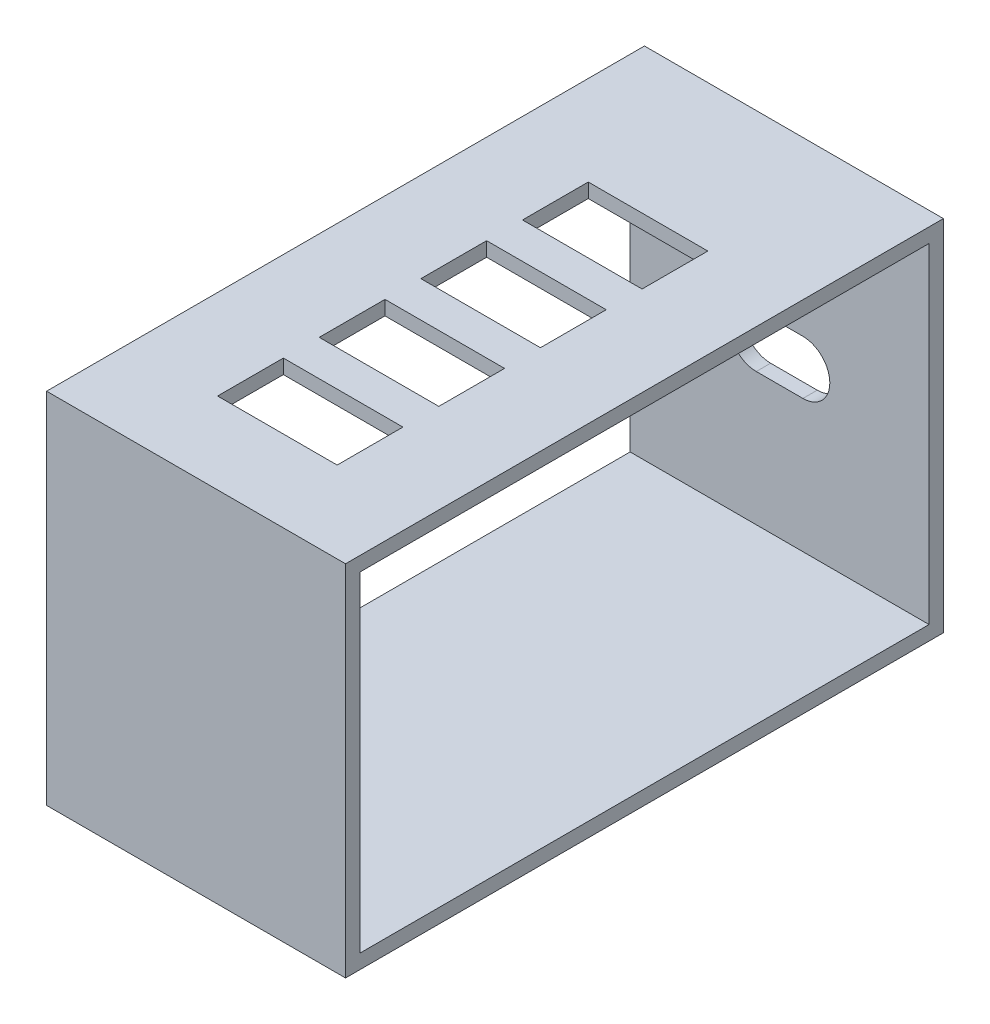
SolidWorks part; units mm, degrees
ref_plane "Front Plane" through (0, 0, 0) normal (0, 0, 1) x (1, 0, 0)
ref_plane "Top Plane" through (0, 0, 0) normal (0, 1, 0) x (1, 0, 0)
ref_plane "Right Plane" through (0, 0, 0) normal (1, 0, 0) x (0, 0, -1)
sketch "Sketch1" plane through (0, 0, 0) normal (1, 0, 0) x (0, 0, -1)
  line L1 (-25, -15) -> (25, -15)
  line L2 (-25, -15) -> (-25, 15)
  line L3 (-25, 15) -> (25, 15)
  line L4 (25, -15) -> (25, 15)
  line L5 (-25, -15) -> (25, 15) construction
  line L6 (-25, 15) -> (25, -15) construction
  point P0 (0, 0)
  dimension "D1" = 50
  dimension "D2" = 30
extrude "Boss-Extrude1" add sketch "Sketch1" along normal mid plane 25
sketch "Sketch2" plane through (-12.5, 0, 0) normal (-1, 0, 0) x (0, 0, 1)
  line L8 (-23.8, 13.8) -> (-23.8, -13.8)
  line L9 (-23.8, -13.8) -> (23.8, -13.8)
  line L10 (23.8, -13.8) -> (23.8, 13.8)
  line L11 (23.8, 13.8) -> (-23.8, 13.8)
  line L12 (-23.8, 13.8) -> (-23.8, -13.8)
  line L13 (-23.8, -13.8) -> (23.8, -13.8)
  line L14 (23.8, -13.8) -> (23.8, 13.8)
  line L15 (23.8, 13.8) -> (-23.8, 13.8)
  dimension "D1" = 1.2
extrude "Cut-Extrude1" cut sketch "Sketch2" against normal up to surface (25 mm away) up to face at (12.5, 0, 0)
sketch "Sketch3" plane through (0, 15, 0) normal (0, 1, 0) x (1, 0, 0)
  line L0 (0, -25) -> (0, 25) construction
  line L1 (12.5, -25) -> (-12.5, -25) construction
  line L2 (12.5, 25) -> (-12.5, 25) construction
  line L3 (5, 7.3) -> (-5, 7.3)
  line L4 (5, 7.3) -> (5, 12.8)
  line L5 (-5, 7.3) -> (-5, 12.8)
  line L6 (5, 12.8) -> (-5, 12.8)
  line L7 (5, 7.3) -> (-5, 12.8) construction
  line L8 (-5, 7.3) -> (5, 12.8) construction
  line L9 (12.5, 23.8) -> (-12.5, 23.8) construction
  line L10 (5, -1.2) -> (-5, -1.2)
  line L11 (5, -1.2) -> (5, 4.3)
  line L12 (5, 4.3) -> (-5, 4.3)
  line L13 (-5, -1.2) -> (-5, 4.3)
  line L14 (0, -33.5) -> (0, 16.5) construction
  line L15 (5, -9.7) -> (-5, -9.7)
  line L16 (5, -9.7) -> (5, -4.2)
  line L17 (5, -4.2) -> (-5, -4.2)
  line L18 (-5, -9.7) -> (-5, -4.2)
  line L19 (0, -42) -> (0, 8) construction
  line L20 (5, -18.2) -> (-5, -18.2)
  line L21 (5, -18.2) -> (5, -12.7)
  line L22 (5, -12.7) -> (-5, -12.7)
  line L23 (-5, -18.2) -> (-5, -12.7)
  line L24 (0, -50.5) -> (0, -0.5) construction
  point P7 (0, 10.05)
  dimension "D1" = 5.5
  dimension "D2" = 11
  dimension "D3" = 10
  dimension "D5" = 3
  dimension "D4" = 4
extrude "Cut-Extrude2" cut sketch "Sketch3" against normal up to surface (1.2 mm away) up to face at (0, 13.8, 0)
sketch "Sketch4" plane through (0, 0, -25) normal (0, 0, -1) x (-1, 0, 0)
  line L0 (0, 15) -> (0, -15) construction
  line L1 (-12.5, 15) -> (12.5, 15) construction
  line L2 (-12.5, -15) -> (12.5, -15) construction
  line L3 (-4.2, 10.8) -> (4.2, 10.8)
  line L4 (-4.2, 10.8) -> (-4.2, 5.8)
  line L5 (4.2, 10.8) -> (4.2, 5.8)
  line L6 (-4.2, 5.8) -> (4.2, 5.8)
  line L7 (-4.2, 10.8) -> (4.2, 5.8) construction
  line L8 (4.2, 10.8) -> (-4.2, 5.8) construction
  line L9 (-1.95, 1.8) -> (1.95, 1.8)
  line L12 (-1.95, -2.7) -> (1.95, -2.7)
  line L13 (-1.95, 1.8) -> (1.95, -2.7) construction
  line L14 (1.95, 1.8) -> (-1.95, -2.7) construction
  line L15 (-12.5, 13.8) -> (12.5, 13.8) construction
  arc A0 (1.95, 1.8) -> (1.95, -2.7) centre (1.95, -0.45) cw
  arc A1 (-1.95, 1.8) -> (-1.95, -2.7) centre (-1.95, -0.45) ccw
  point P7 (0, 8.3)
  point P8 (0, -0.45)
  point P20 (-4.2, -0.45)
  point P21 (4.2, -0.45)
  point P22 (0, 0)
  dimension "D1" = 5
  dimension "D2" = 3
  dimension "D3" = 8.4
  dimension "D4" = 8.4
  dimension "D5" = 4.5
  dimension "D6" = 12
extrude "Cut-Extrude3" cut sketch "Sketch4" against normal up to surface (1.2 mm away) up to face at (0, 0, -23.8)
